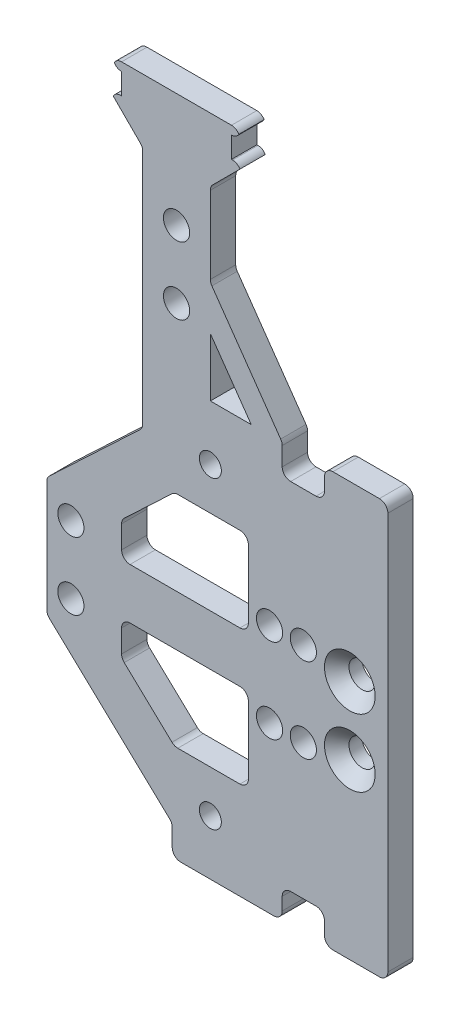
SolidWorks part; units mm, degrees
material "环氧树脂板"
ref_plane "前视基准面" through (0, 0, 0) normal (0, 0, 1) x (1, 0, 0)
ref_plane "上视基准面" through (0, 0, 0) normal (0, 1, 0) x (1, 0, 0)
ref_plane "右视基准面" through (0, 0, 0) normal (1, 0, 0) x (0, 0, -1)
sketch "草图1" plane through (0, 0, 0) normal (0, 0, 1) x (1, 0, 0)
  line L0 (0, 0) -> (0, 18) construction
  line L1 (16.5, -4) -> (-16.5, -4) construction
  line L2 (16.5, -4) -> (16.5, 4) construction
  line L3 (16.5, 4) -> (-16.5, 4) construction
  line L4 (-16.5, -4) -> (-16.5, 4) construction
  line L5 (16.5, -4) -> (-16.5, 4) construction
  line L6 (16.5, 4) -> (-16.5, -4) construction
  line L7 (0, 0) -> (2.3681, 0) construction
  line L8 (-19.35, 7) -> (-19.35, -7) construction
  line L9 (-19.35, -7) -> (-4.5091, -21)
  line L10 (-4.5091, -21) -> (4.5091, -21) construction
  line L11 (4.5091, -21) -> (13.5197, -12.5) construction
  line L12 (21, -5.4435) -> (21, 5.4435)
  line L13 (13.5197, 12.5) -> (4.5091, 21) construction
  line L14 (4.5091, 21) -> (-4.5091, 21) construction
  line L15 (-4.5091, 21) -> (-10.85, 15.0184) construction
  line L16 (13.5197, 12.5) -> (21, 12.5) construction
  line L17 (21, 12.5) -> (21, 5.4435)
  line L18 (13.5197, -12.5) -> (21, -12.5) construction
  line L19 (21, -12.5) -> (21, -5.4435)
  line L20 (-4.5091, 21) -> (-4.5091, 24.5) construction
  line L21 (0, 24.5) -> (4.8377, 24.5)
  line L22 (21, 24.5) -> (21, 12.5)
  line L23 (21, -24.5) -> (21, -12.5)
  line L24 (-4.5091, -24.5) -> (8.5, -24.5)
  line L25 (-4.5091, -21) -> (-4.5091, -24.5)
  line L26 (13.5, -29) -> (8.5, -29) construction
  line L27 (13.5, 21) -> (8.5, 21)
  line L28 (13.5, 21) -> (13.5, 29) construction
  line L29 (13.5, 29) -> (8.5, 29) construction
  line L30 (8.5, 21) -> (8.5, 29) construction
  line L31 (13.5, 21) -> (8.5, 29) construction
  line L32 (13.5, 29) -> (8.5, 21) construction
  line L33 (8.5, -21) -> (8.5, -29) construction
  line L34 (13.5, -21) -> (8.5, -21) construction
  line L35 (13.5, -21) -> (13.5, -29) construction
  line L36 (8.5, -25) -> (6.3492, -25) construction
  line L37 (13.5, 21) -> (13.5, 24.5)
  line L38 (8.5, 21) -> (8.5, 24.5)
  line L39 (13.5, 24.5) -> (21, 24.5)
  line L40 (8.5, -24.5) -> (8.5, -21)
  line L41 (8.5, -21) -> (13.5, -21)
  line L42 (13.5, -21) -> (13.5, -24.5)
  line L43 (13.5, -24.5) -> (21, -24.5)
  line L44 (-4.2458, 13) -> (4.5, 13)
  line L45 (4.5, 13) -> (4.5, 3)
  line L46 (4.5, 3) -> (-10.5, 3)
  line L47 (-10.5, 3) -> (-10.5, 7.1002)
  line L48 (-10.5, 7.1002) -> (-4.2458, 13)
  line L49 (-10.5, -3) -> (-10.5, -7.1002)
  line L50 (4.5, -3) -> (-10.5, -3)
  line L51 (4.5, -13) -> (4.5, -3)
  line L52 (-4.2458, -13) -> (4.5, -13)
  line L53 (-10.5, -7.1002) -> (-4.2458, -13)
  line L55 (-26, 30) -> (-18, 30) construction
  line L57 (-17.85, 8.415) -> (-19.35, 7) construction
  line L58 (-26, 30) -> (-26, 14) construction
  line L59 (-26, 14) -> (-17.85, 14) construction
  line L60 (-17.85, 14) -> (-17.85, 8.415) construction
  line L61 (-18, 30) -> (-18, 21) construction
  line L62 (-18, 21) -> (-10.85, 21) construction
  line L63 (-10.85, 21) -> (-10.85, 15.0184) construction
  line L64 (-18, 30) -> (-13.85, 24.7762) construction
  line L66 (-13.85, 24.7762) -> (-13.85, 21) construction
  line L67 (-13.85, 21) -> (-10.85, 21) construction
  line L68 (-26, 14) -> (-19.35, 5.6294) construction
  line L69 (-19.35, 5.6294) -> (-19.35, -7)
  line L70 (-19.35, 5.6294) -> (-19.35, 7)
  line L71 (-19.35, 7) -> (-10.85, 15.0184)
  line L73 (-8, 46.5) -> (0, 46.5) construction
  line L74 (0, 46.5) -> (0, 36.6393)
  line L75 (-8, 46.5) -> (-8, 17.7069)
  line L76 (-10.85, 15.0184) -> (-8, 17.7069)
  line L77 (0, 36.6393) -> (8.5, 24.5)
  line L78 (0, 31.4089) -> (4.8377, 24.5)
  line L79 (0, 31.4089) -> (0, 24.5)
  line L80 (-8, 46.5) -> (-11.5, 50)
  line L81 (-11.5, 50) -> (-11.5, 50.5)
  line L82 (-11.5, 54) -> (3.5, 54)
  line L83 (-11.5, 53) -> (-10.5, 53)
  line L84 (3.5, 54) -> (3.5, 50) construction
  line L85 (3.5, 50) -> (0, 46.5)
  line L86 (-10.5, 53) -> (-10.5, 50.5)
  line L87 (-10.5, 50.5) -> (-11.5, 50.5)
  line L88 (-4, 40.5) -> (-4, 42.3981) construction
  line L89 (2.5, 50.5) -> (3.5, 50.5)
  line L90 (2.5, 53) -> (2.5, 50.5)
  line L91 (3.5, 53) -> (2.5, 53)
  line L92 (-11.5, 53) -> (-11.5, 54)
  line L93 (3.5, 54) -> (3.5, 53)
  line L94 (3.5, 50.5) -> (3.5, 50)
  circle A0 centre (-16.5, 4) radius 1.55
  circle A1 centre (-16.5, -4) radius 1.55
  circle A2 centre (16.5, 4) radius 1.55
  circle A3 centre (16.5, -4) radius 1.55
  circle A4 centre (0, 18) radius 1.3
  circle A5 centre (0, -18) radius 1.3
  circle A6 centre (-22, 26) radius 1.55 construction
  circle A7 centre (-22, 18) radius 1.55 construction
  circle A8 centre (-4, 40.5) radius 1.55
  circle A9 centre (-4, 32.5) radius 1.55
  point P0 (0, 0)
  point P32 (11, 25)
  dimension "D1" = 36
  dimension "D4" = 3.1
  dimension "D9" = 2.6
  dimension "D22" = 3.1
  dimension "D35" = 3.1
  dimension "D2" = 33
  dimension "D3" = 8
  dimension "D5" = 3
  dimension "D6" = 4.5
  dimension "D7" = 46.67
  dimension "D8" = 14
  dimension "D10" = 25
  dimension "D11" = 2.85
  dimension "D12" = 3.5
  dimension "D13" = 11
  dimension "D14" = 50
  dimension "D15" = 8
  dimension "D16" = 5
  dimension "D17" = 6
  dimension "D18" = 5
  dimension "D19" = 6
  dimension "D20" = 6
  dimension "D21" = 12
  dimension "D23" = 8
  dimension "D24" = 22
  dimension "D25" = 4
  dimension "D26" = 8
  dimension "D27" = 18
  dimension "D28" = 4
  dimension "D29" = 1.5
  dimension "D30" = 4
  dimension "D31" = 7
  dimension "D32" = 7
  dimension "D33" = 3
  dimension "D34" = 8
  dimension "D36" = 4
  dimension "D37" = 8
  dimension "D38" = 8
  dimension "D39" = 6
  dimension "D40" = 4
  dimension "D41" = 3
  dimension "D42" = 55
  dimension "D43" = 15
  dimension "D44" = 45
  dimension "D45" = 45
  dimension "D46" = 2.5
  dimension "D47" = 1
  dimension "D48" = 4
  dimension "D49" = 1
extrude "凸台-拉伸1" add sketch "草图1" along normal blind 3
sketch "草图3" plane through (0, 0, 3) normal (0, 0, 1) x (1, 0, 0)
  line L0 (0, 0) -> (6.5902, 0) construction
  circle A0 centre (0, 18) radius 1.3 construction
  circle A1 centre (11, 5) radius 1.55
  circle A2 centre (7, 5) radius 1.55
  circle A3 centre (11, -5) radius 1.55
  circle A4 centre (7, -5) radius 1.55
  dimension "D3" = 3.1
  dimension "D1" = 10
  dimension "D2" = 11
  dimension "D4" = 4
extrude "切除-拉伸1" cut sketch "草图3" against normal through all
hole_wizard "M3 六角凹锥坑螺钉的锥形沉头孔1" positions "3D草图1" profile "草图4" countersink size "M3" standard "ISO" end condition through all
sketch3d "3D草图1"
  line L0 (16.5, -4, 3) -> (16.5, -4, 0) construction
  line L1 (16.5, 4, 3) -> (16.5, 4, 0) construction
  point P4 (16.5, 4, 3)
  point P8 (16.5, -4, 3)
sketch "草图4" plane through (16.5, -4, 3) normal (1, 0, 0) x (0, -1, 0)
  line L0 (0, 0) -> (0, 3)
  line L1 (0, 3) -> (1.55, 3)
  line L2 (1.55, 3) -> (1.55, 1.45)
  line L3 (1.55, 1.45) -> (3, 0)
  line L5 (3, 0) -> (0, 0)
  line L6 (-1.55, 1.45) -> (-3, 0) construction
  line L11 (0, -6.35) -> (0, 107.95) construction
  dimension "通孔孔直径" = 3.1
  dimension "通孔孔深度" = 3
  dimension "近端锥形沉头孔直径" = 6
  dimension "近端锥形沉头孔角度" = 90
fillet "圆角1" radius 1 34 edges at (8.5, 21, 1.5) (13.5, 21, 1.5) (13.5, 24.5, 1.5) (21, 24.5, 1.5) (21, -24.5, 1.5) (13.5, -24.5, 1.5) (13.5, -21, 1.5) (8.5, -21, 1.5) (8.5, -24.5, 1.5) (-4.5091, -24.5, 1.5) (-4.5091, -21, 1.5) (-10.5, -7.1002, 1.5) (-4.2458, -13, 1.5) (4.5, -13, 1.5) (4.5, -3, 1.5) (-10.5, -3, 1.5) (-10.5, 3, 1.5) (4.5, 3, 1.5) (4.5, 13, 1.5) (-10.5, 7.1002, 1.5) (-4.2458, 13, 1.5) (-19.35, -7, 1.5) (-19.35, 7, 1.5) (-8, 17.7069, 1.5) (-8, 46.5, 1.5) (-11.5, 50.5, 1.5) (-11.5, 53, 1.5) (-11.5, 54, 1.5) (3.5, 54, 1.5) (3.5, 53, 1.5) (3.5, 50.5, 1.5) (0, 36.6393, 1.5) (8.5, 24.5, 1.5) (0, 46.5, 1.5)
